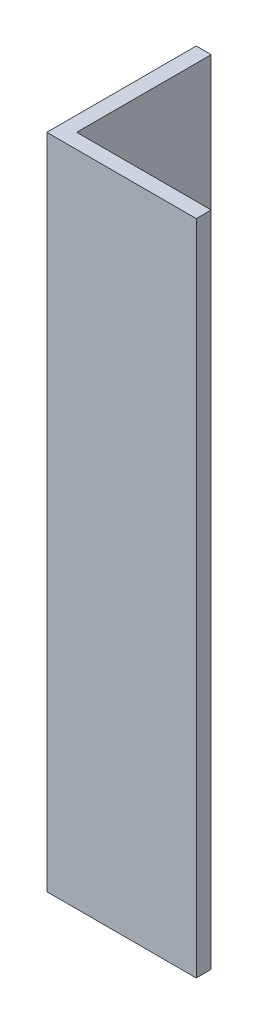
SolidWorks part; units mm, degrees
material "1060 Alloy"
ref_plane "Front Plane" through (0, 0, 0) normal (0, 0, 1) x (1, 0, 0)
ref_plane "Top Plane" through (0, 0, 0) normal (0, 1, 0) x (1, 0, 0)
ref_plane "Right Plane" through (0, 0, 0) normal (1, 0, 0) x (0, 0, -1)
sketch "Sketch1" plane through (0, 0, 0) normal (0, 1, 0) x (1, 0, 0)
  line L1 (0, 0) -> (20, 0)
  line L2 (0, 0) -> (0, 20)
  line L3 (0, 20) -> (2, 20)
  line L4 (20, 0) -> (20, 2)
  line L7 (20, 2) -> (2, 2)
  line L8 (2, 20) -> (2, 2)
  dimension "D1" = 20
  dimension "D2" = 20
  dimension "D3" = 2
  dimension "D4" = 2
extrude "Boss-Extrude1" add sketch "Sketch1" along normal blind 44 and the other way blind 44
